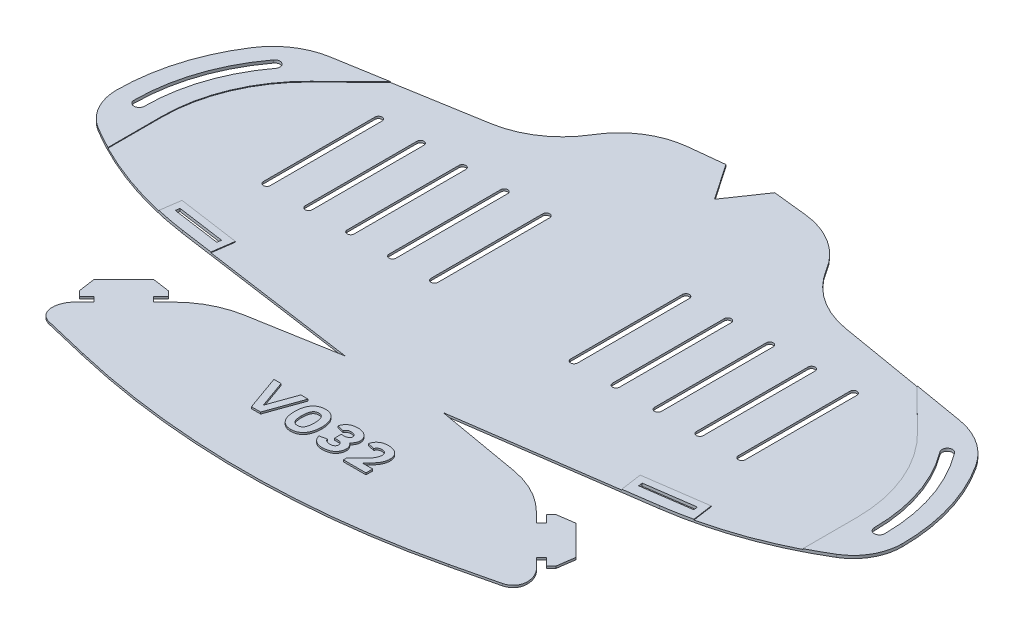
SolidWorks part; units mm, degrees
ref_plane "Front Plane" through (0, 0, 0) normal (0, 0, 1) x (1, 0, 0)
ref_plane "Top Plane" through (0, 0, 0) normal (0, 1, 0) x (1, 0, 0)
ref_plane "Right Plane" through (0, 0, 0) normal (1, 0, 0) x (0, 0, -1)
sketch "Sketch1" plane through (0, 0, 0) normal (0, 1, 0) x (1, 0, 0)
  line L0 (0, 0) -> (0, -145) construction
  line L1 (-14, -102) -> (14, -102) construction
  line L2 (-112.5, -69) -> (112.5, -69) construction
  line L3 (0, -10.2352) -> (-7, 0)
  line L4 (0, -10.2352) -> (7, 0)
  line L5 (7, 0) -> (16.9419, -1.0768)
  line L6 (-90.1804, -30.1909) -> (-50.7439, -23.5)
  line L7 (90.1804, -30.1909) -> (50.7439, -23.5)
  line L8 (-14, -102) -> (-68.2662, -94.2919)
  line L9 (-7, 0) -> (-16.9419, -1.0768)
  line L10 (14, -102) -> (68.2662, -94.2919)
  line L11 (-103.5977, -39) -> (-103.5977, -69) construction
  line L12 (-14, -102) -> (-38.6266, -106.305)
  line L13 (-52, -113.2546) -> (-54.8283, -116.0832)
  line L14 (52, -113.2546) -> (54.8283, -116.0832)
  line L15 (14, -102) -> (38.6266, -106.305)
  line L16 (-54.8283, -116.0832) -> (-56.2426, -114.669)
  line L17 (-56.2426, -114.669) -> (-54.1214, -112.5476)
  line L18 (-54.1214, -112.5476) -> (-55.5356, -111.1334)
  line L19 (-55.5356, -111.1334) -> (-60.4854, -110.4265)
  line L20 (-60.4854, -110.4265) -> (-68.9703, -118.9122)
  line L21 (-64.7275, -123.1546) -> (-63.3132, -124.5688)
  line L22 (-63.3132, -124.5688) -> (-66.1415, -127.3973)
  line L23 (-64.7275, -123.1546) -> (-66.8487, -125.2761)
  line L24 (-66.8487, -125.2761) -> (-68.263, -123.8619)
  line L25 (-68.9703, -118.9122) -> (-68.263, -123.8619)
  line L26 (68.9703, -118.9122) -> (68.263, -123.8619)
  line L27 (66.8487, -125.2761) -> (68.263, -123.8619)
  line L28 (64.7275, -123.1546) -> (66.8487, -125.2761)
  line L29 (63.3132, -124.5688) -> (66.1415, -127.3973)
  line L30 (64.7275, -123.1546) -> (63.3132, -124.5688)
  line L31 (60.4854, -110.4265) -> (68.9703, -118.9122)
  line L32 (55.5356, -111.1334) -> (60.4854, -110.4265)
  line L33 (54.1214, -112.5476) -> (55.5356, -111.1334)
  line L34 (56.2426, -114.669) -> (54.1214, -112.5476)
  line L35 (54.8283, -116.0832) -> (56.2426, -114.669)
  line L36 (-64.9691, -135.8852) -> (-52.4361, -138.8607)
  line L37 (64.9691, -135.8852) -> (52.4361, -138.8607)
  line L38 (-68.9703, -118.9122) -> (-64.7275, -123.1546) construction
  line L39 (-60.4854, -110.4265) -> (-56.2426, -114.669) construction
  arc A0 (-16.9419, -1.0768) -> (-33.4614, -11.6696) centre (-14.5729, -22.9489) ccw
  arc A1 (-33.4614, -11.6696) -> (-50.7439, -23.5) centre (-54.9257, 1.1478) cw
  arc A2 (-103.5977, -39) -> (-90.1804, -30.1909) centre (-86.8349, -49.9091) cw
  arc A3 (-112.5, -69) -> (-103.5977, -39) centre (-57.5, -69) cw
  arc A4 (112.5, -69) -> (103.5977, -39) centre (57.5, -69) ccw
  arc A5 (103.5977, -39) -> (90.1804, -30.1909) centre (86.8349, -49.9091) ccw
  arc A6 (16.9419, -1.0768) -> (33.4614, -11.6696) centre (14.5729, -22.9489) cw
  arc A7 (33.4614, -11.6696) -> (50.7439, -23.5) centre (54.9257, 1.1478) ccw
  arc A8 (-112.5, -69) -> (-105.7111, -81) centre (-98.5, -69) ccw
  arc A9 (-105.7111, -81) -> (-68.2662, -94.2919) centre (-54.2032, 4.7143) ccw
  arc A10 (112.5, -69) -> (105.7111, -81) centre (98.5, -69) cw
  arc A11 (105.7111, -81) -> (68.2662, -94.2919) centre (54.2032, 4.7143) cw
  arc A12 (-38.6266, -106.305) -> (-52, -113.2546) centre (-34.3216, -130.9315) ccw
  arc A13 (38.6266, -106.305) -> (52, -113.2546) centre (34.3216, -130.9315) cw
  arc A14 (-66.1415, -127.3973) -> (-68.0451, -131.9933) centre (-61.5451, -131.9933) ccw
  arc A15 (-68.0451, -131.9933) -> (-64.9691, -135.8852) centre (-64.0451, -131.9933) ccw
  arc A16 (68.0451, -131.9933) -> (64.9691, -135.8852) centre (64.0451, -131.9933) cw
  arc A17 (66.1415, -127.3973) -> (68.0451, -131.9933) centre (61.5451, -131.9933) cw
  arc A19 (-52.4361, -138.8607) -> (0, -145) centre (0, 82) ccw
  arc A20 (52.4361, -138.8607) -> (0, -145) centre (0, 82) cw
  point P8 (0, -102)
  point P11 (0, -69)
  dimension "D5" = 55
  dimension "D11" = 20
  dimension "D13" = 25
  dimension "D16" = 14
  dimension "D15" = 22
  dimension "D18" = 100
  dimension "D22" = 25
  dimension "D31" = 6.5
  dimension "D32" = 4
  dimension "D34" = 227
  dimension "D1" = 145
  dimension "D2" = 28
  dimension "D3" = 43
  dimension "D4" = 76
  dimension "D6" = 225
  dimension "D7" = 14
  dimension "D8" = 12.4
  dimension "D9" = 10
  dimension "D10" = 30
  dimension "D12" = 40
  dimension "D14" = 45.5
  dimension "D17" = 12
  dimension "D19" = 18
  dimension "D20" = 25
  dimension "D21" = 4
  dimension "D23" = 38
  dimension "D24" = 2
  dimension "D25" = 3
  dimension "D26" = 2
  dimension "D27" = 18
  dimension "D29" = 8
  dimension "D30" = 4
extrude "Main Shape" add sketch "Sketch1" along normal blind 0.6
sketch "Sketch2" plane through (0, 0.6, 0) normal (0, 1, 0) x (1, 0, 0)
  line L0 (0, -55) -> (0, 55) construction
  arc A0 (-96.3, -39.9) -> (-106, -69) centre (-57.5, -69) ccw construction
  arc A1 (-97.5, -39) -> (-107.5, -69) centre (-57.5, -69) ccw
  arc A2 (-95.1, -40.8) -> (-104.5, -69) centre (-57.5, -69) ccw
  arc A3 (-95.1, -40.8) -> (-97.5, -39) centre (-96.3, -39.9) ccw
  arc A4 (-107.5, -69) -> (-104.5, -69) centre (-106, -69) ccw
  arc A6 (-103.5977, -39) -> (-112.5, -69) centre (-57.5, -69) ccw construction
  arc A7 (96.3, -39.9) -> (106, -69) centre (57.5, -69) cw construction
  arc A8 (97.5, -39) -> (107.5, -69) centre (57.5, -69) cw
  arc A9 (95.1, -40.8) -> (104.5, -69) centre (57.5, -69) cw
  arc A10 (95.1, -40.8) -> (97.5, -39) centre (96.3, -39.9) cw
  arc A11 (107.5, -69) -> (104.5, -69) centre (106, -69) cw
  point P3 (-103.5111, -53.663)
  point P19 (103.5111, -53.663)
  dimension "D1" = 5
  dimension "D2" = 1.5
extrude "Elastic Attachment Points" cut sketch "Sketch2" against normal through all
sketch "Sketch7" plane through (0, 0.6, 0) normal (0, 1, 0) x (1, 0, 0)
  line L0 (-99.5, -69) -> (-99.5, -84.4384)
  line L1 (-86.8939, -39) -> (-75.3319, -27.6717)
  line L2 (-50.7439, -23.5) -> (-90.1804, -30.1909) construction
  line L3 (-75.3319, -27.6717) -> (-90.1804, -30.1909)
  line L4 (0, -55) -> (0, 55) construction
  line L5 (75.3319, -27.6717) -> (90.1804, -30.1909)
  line L6 (86.8939, -39) -> (75.3319, -27.6717)
  line L7 (99.5, -69) -> (99.5, -84.4384)
  arc A0 (-99.5, -69) -> (-86.8939, -39) centre (-57.5, -69) cw
  arc A1 (-95.1, -40.8) -> (-104.5, -69) centre (-57.5, -69) ccw construction
  arc A2 (-105.7111, -81) -> (-68.2662, -94.2919) centre (-54.2032, 4.7143) ccw construction
  arc A3 (-112.5, -69) -> (-105.7111, -81) centre (-98.5, -69) ccw construction
  arc A4 (-103.5977, -39) -> (-112.5, -69) centre (-57.5, -69) ccw construction
  arc A5 (-90.1804, -30.1909) -> (-103.5977, -39) centre (-86.8349, -49.9091) ccw construction
  arc A6 (-105.7111, -81) -> (-99.5, -84.4384) centre (-54.2032, 4.7143) ccw
  arc A7 (-112.5, -69) -> (-105.7111, -81) centre (-98.5, -69) ccw
  arc A8 (-103.5977, -39) -> (-112.5, -69) centre (-57.5, -69) ccw
  arc A9 (-90.1804, -30.1909) -> (-103.5977, -39) centre (-86.8349, -49.9091) ccw
  arc A10 (90.1804, -30.1909) -> (103.5977, -39) centre (86.8349, -49.9091) cw
  arc A11 (103.5977, -39) -> (112.5, -69) centre (57.5, -69) cw
  arc A12 (112.5, -69) -> (105.7111, -81) centre (98.5, -69) cw
  arc A13 (105.7111, -81) -> (99.5, -84.4384) centre (54.2032, 4.7143) cw
  arc A14 (99.5, -69) -> (86.8939, -39) centre (57.5, -69) ccw
  arc A15 (-107.5, -69) -> (-104.5, -69) centre (-106, -69) ccw construction
  arc A16 (-95.1, -40.8) -> (-97.5, -39) centre (-96.3, -39.9) ccw construction
  arc A17 (-97.5, -39) -> (-107.5, -69) centre (-57.5, -69) ccw construction
  arc A18 (-107.5, -69) -> (-104.5, -69) centre (-106, -69) ccw
  arc A19 (-95.1, -40.8) -> (-97.5, -39) centre (-96.3, -39.9) ccw
  arc A20 (-95.1, -40.8) -> (-104.5, -69) centre (-57.5, -69) ccw
  arc A21 (-97.5, -39) -> (-107.5, -69) centre (-57.5, -69) ccw
  arc A22 (104.5, -69) -> (107.5, -69) centre (106, -69) ccw construction
  arc A23 (97.5, -39) -> (95.1, -40.8) centre (96.3, -39.9) ccw construction
  arc A24 (104.5, -69) -> (95.1, -40.8) centre (57.5, -69) ccw construction
  arc A25 (107.5, -69) -> (97.5, -39) centre (57.5, -69) ccw construction
  arc A26 (104.5, -69) -> (107.5, -69) centre (106, -69) ccw
  arc A27 (97.5, -39) -> (95.1, -40.8) centre (96.3, -39.9) ccw
  arc A28 (104.5, -69) -> (95.1, -40.8) centre (57.5, -69) ccw
  arc A29 (107.5, -69) -> (97.5, -39) centre (57.5, -69) ccw
  dimension "D1" = 5
extrude "Reinforced Attachment Points" add sketch "Sketch7" along normal blind 0.2
sketch "Sketch6" plane through (0, 0.6, 0) normal (0, 1, 0) x (1, 0, 0)
  line L0 (-74.2491, -90.412) -> (-60.3883, -92.3808)
  line L1 (-60.3883, -92.3808) -> (-60.2195, -91.1927)
  line L2 (-60.2195, -91.1927) -> (-74.0804, -89.2239)
  line L3 (-74.0804, -89.2239) -> (-74.2491, -90.412)
  line L4 (-68.2662, -94.2919) -> (-14, -102) construction
  line L5 (-67.1499, -90.2083) -> (-67.3187, -91.3964) construction
  line L13 (0, -0.44) -> (0, 0.44) construction
  line L14 (67.1499, -90.2083) -> (67.3187, -91.3964) construction
  line L15 (74.2491, -90.412) -> (74.0804, -89.2239)
  line L16 (60.2195, -91.1927) -> (60.3883, -92.3808)
  line L22 (60.2195, -91.1927) -> (74.0804, -89.2239)
  line L24 (74.2491, -90.412) -> (60.3883, -92.3808)
  dimension "D1" = 3
  dimension "D2" = 14
  dimension "D3" = 54.28
  dimension "D4" = 1.2
extrude "Tab Slits" cut sketch "Sketch6" against normal through all
sketch "Sketch9" plane through (0, 0.6, 0) normal (0, 1, 0) x (1, 0, 0)
  line L4 (-60.3883, -92.3808) -> (-60.2195, -91.1927) construction
  line L5 (-74.2491, -90.412) -> (-60.3883, -92.3808) construction
  line L6 (-74.0804, -89.2239) -> (-74.2491, -90.412) construction
  line L7 (-60.2195, -91.1927) -> (-74.0804, -89.2239) construction
  line L12 (-60.3883, -92.3808) -> (-60.2195, -91.1927)
  line L13 (-74.2491, -90.412) -> (-60.3883, -92.3808)
  line L14 (-74.0804, -89.2239) -> (-74.2491, -90.412)
  line L15 (-60.2195, -91.1927) -> (-74.0804, -89.2239)
  line L16 (-58.83, -95.6323) -> (-57.9581, -89.4939)
  line L17 (-68.2662, -94.2919) -> (-14, -102) construction
  line L18 (-57.9581, -89.4939) -> (-75.7792, -86.9625)
  line L19 (-75.7792, -86.9625) -> (-76.6006, -92.7452)
  line L20 (-68.2662, -94.2919) -> (-58.83, -95.6323)
  line L21 (0, -0.605) -> (0, 0.605) construction
  line L22 (68.2662, -94.2919) -> (58.83, -95.6323)
  line L23 (75.7792, -86.9625) -> (76.6006, -92.7452)
  line L24 (57.9581, -89.4939) -> (75.7792, -86.9625)
  line L25 (58.83, -95.6323) -> (57.9581, -89.4939)
  line L26 (60.2195, -91.1927) -> (74.0804, -89.2239)
  line L27 (74.0804, -89.2239) -> (74.2491, -90.412)
  line L28 (74.2491, -90.412) -> (60.3883, -92.3808)
  line L29 (60.3883, -92.3808) -> (60.2195, -91.1927)
  arc A0 (-99.5, -84.4384) -> (-68.2662, -94.2919) centre (-54.2032, 4.7143) ccw construction
  arc A1 (-76.6006, -92.7452) -> (-68.2662, -94.2919) centre (-54.2032, 4.7143) ccw
  arc A2 (76.6006, -92.7452) -> (68.2662, -94.2919) centre (54.2032, 4.7143) cw
  dimension "D1" = 2
  dimension "D2" = 2
  dimension "D3" = 2
extrude "Reinforced Tab Slits" add sketch "Sketch9" along normal blind 0.2
sketch "Sketch3" plane through (0, 0.6, 0) normal (0, 1, 0) x (1, 0, 0)
  line L0 (-20, -38.45) -> (-20, -70.45) construction
  line L1 (-19, -38.45) -> (-19, -70.45)
  line L2 (-21, -38.45) -> (-21, -70.45)
  line L3 (0, -10.2352) -> (0, -145) construction
  line L4 (-106, -69) -> (-96.3, -69) construction
  line L5 (-96.3, -69) -> (-96.3, -39.9) construction
  line L6 (-32, -38.45) -> (-32, -70.45) construction
  line L7 (-31, -38.45) -> (-31, -70.45)
  line L8 (-33, -38.45) -> (-33, -70.45)
  line L9 (-44, -38.45) -> (-44, -70.45) construction
  line L10 (-43, -38.45) -> (-43, -70.45)
  line L11 (-45, -38.45) -> (-45, -70.45)
  line L12 (-56, -38.45) -> (-56, -70.45) construction
  line L13 (-55, -38.45) -> (-55, -70.45)
  line L14 (-57, -38.45) -> (-57, -70.45)
  line L15 (-68, -38.45) -> (-68, -70.45) construction
  line L16 (-67, -38.45) -> (-67, -70.45)
  line L17 (-69, -38.45) -> (-69, -70.45)
  line L18 (20, -38.45) -> (20, -70.45) construction
  line L19 (19, -38.45) -> (19, -70.45)
  line L20 (21, -38.45) -> (21, -70.45)
  line L21 (32, -38.45) -> (32, -70.45) construction
  line L22 (31, -38.45) -> (31, -70.45)
  line L23 (33, -38.45) -> (33, -70.45)
  line L24 (44, -38.45) -> (44, -70.45) construction
  line L25 (43, -38.45) -> (43, -70.45)
  line L26 (45, -38.45) -> (45, -70.45)
  line L27 (56, -38.45) -> (56, -70.45) construction
  line L28 (55, -38.45) -> (55, -70.45)
  line L29 (57, -38.45) -> (57, -70.45)
  line L30 (68, -38.45) -> (68, -70.45) construction
  line L31 (67, -38.45) -> (67, -70.45)
  line L32 (69, -38.45) -> (69, -70.45)
  arc A0 (-19, -38.45) -> (-21, -38.45) centre (-20, -38.45) ccw
  arc A1 (-21, -70.45) -> (-19, -70.45) centre (-20, -70.45) ccw
  arc A2 (-52.4361, -138.8607) -> (52.4361, -138.8607) centre (0, 82) ccw construction
  arc A3 (-31, -38.45) -> (-33, -38.45) centre (-32, -38.45) ccw
  arc A4 (-33, -70.45) -> (-31, -70.45) centre (-32, -70.45) ccw
  arc A5 (-43, -38.45) -> (-45, -38.45) centre (-44, -38.45) ccw
  arc A6 (-45, -70.45) -> (-43, -70.45) centre (-44, -70.45) ccw
  arc A7 (-55, -38.45) -> (-57, -38.45) centre (-56, -38.45) ccw
  arc A8 (-57, -70.45) -> (-55, -70.45) centre (-56, -70.45) ccw
  arc A9 (-67, -38.45) -> (-69, -38.45) centre (-68, -38.45) ccw
  arc A10 (-69, -70.45) -> (-67, -70.45) centre (-68, -70.45) ccw
  arc A11 (19, -38.45) -> (21, -38.45) centre (20, -38.45) cw
  arc A12 (21, -70.45) -> (19, -70.45) centre (20, -70.45) cw
  arc A13 (31, -38.45) -> (33, -38.45) centre (32, -38.45) cw
  arc A14 (33, -70.45) -> (31, -70.45) centre (32, -70.45) cw
  arc A15 (43, -38.45) -> (45, -38.45) centre (44, -38.45) cw
  arc A16 (45, -70.45) -> (43, -70.45) centre (44, -70.45) cw
  arc A17 (55, -38.45) -> (57, -38.45) centre (56, -38.45) cw
  arc A18 (57, -70.45) -> (55, -70.45) centre (56, -70.45) cw
  arc A19 (67, -38.45) -> (69, -38.45) centre (68, -38.45) cw
  arc A20 (69, -70.45) -> (67, -70.45) centre (68, -70.45) cw
  point P2 (-20, -54.45)
  point P13 (-19, -54.45)
  point P16 (-96.3, -54.45)
  point P20 (-32, -54.45)
  point P31 (-44, -54.45)
  point P38 (-56, -54.45)
  point P45 (-68, -54.45)
  point P52 (20, -54.45)
  point P59 (32, -54.45)
  point P66 (44, -54.45)
  point P73 (56, -54.45)
  point P80 (68, -54.45)
  dimension "D1" = 2
  dimension "D2" = 32
  dimension "D3" = 20
  dimension "D4" = 5
  dimension "D5" = 10
extrude "Breathing Slits" cut sketch "Sketch3" against normal through all
sketch "Sketch8" plane through (0, 0.6, 0) normal (0, 1, 0) x (1, 0, 0)
  line L0 (-67.0266, -128.5) -> (67.0266, -128.5) construction
  line L1 (0, -10.2352) -> (0, -145) construction
  arc A0 (-52.4361, -138.8607) -> (52.4361, -138.8607) centre (0, 82) ccw construction
  arc A1 (-66.1415, -127.3973) -> (-68.0451, -131.9933) centre (-61.5451, -131.9933) ccw construction
  text T0 "<b>V032</b>" font "Double Porter 3" height 10
  point P9 (0, -128.5)
  dimension "D2" = 16.5
extrude "Version Number" add sketch "Sketch8" along normal blind 0.5
